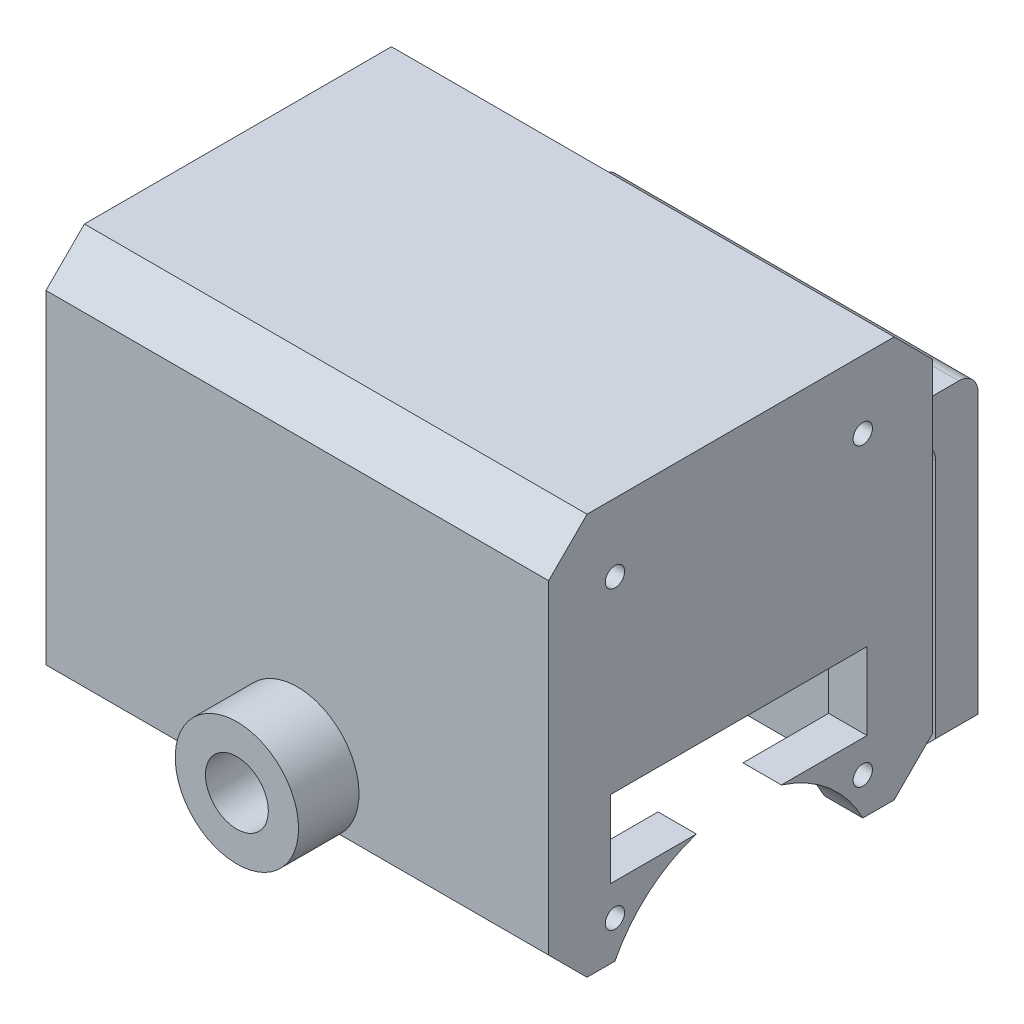
SolidWorks part; units mm, degrees
material "PLA"
ref_plane "Front Plane" through (0, 0, 0) normal (0, 0, 1) x (1, 0, 0)
ref_plane "Top Plane" through (0, 0, 0) normal (0, 1, 0) x (1, 0, 0)
ref_plane "Right Plane" through (0, 0, 0) normal (1, 0, 0) x (0, 0, -1)
sketch "Sketch1" plane through (0, 0, 0) normal (1, 0, 0) x (0, 0, -1)
  line L1 (0, 0) -> (25, 0)
  line L2 (0, 0) -> (0, 30)
  line L3 (0, 30) -> (25, 30)
  line L4 (25, 0) -> (25, 30)
  dimension "D1" = 30
  dimension "D2" = 25
extrude "Boss-Extrude1" add sketch "Sketch1" along normal blind 3.175
sketch "Sketch2" plane through (0, 0, 0) normal (-1, 0, 0) x (0, 0, 1)
  line L1 (-25, 30) -> (0, 30)
  line L2 (-25, 30) -> (-25, 33.175)
  line L3 (-25, 33.175) -> (0, 33.175)
  line L4 (0, 30) -> (0, 33.175)
  dimension "D1" = 3.175
extrude "Boss-Extrude2" add sketch "Sketch2" against normal blind 41.58
sketch "Sketch3" plane through (0, 30, 0) normal (0, -1, 0) x (1, 0, 0)
  line L0 (41.58, 0) -> (3.175, 0) construction
  line L1 (41.58, -25) -> (38.405, -25)
  line L2 (41.58, -25) -> (41.58, 0)
  line L3 (41.58, 0) -> (38.405, 0)
  line L4 (38.405, -25) -> (38.405, 0)
  dimension "D1" = 3.175
extrude "Boss-Extrude3" add sketch "Sketch3" along normal up to surface (30 mm away) up to face at (1.5875, 0, -12.5)
sketch "Sketch4" plane through (0, 0, 0) normal (-1, 0, 0) x (0, 0, 1)
  circle A0 centre (-12.36, -5.21) radius 11.5
  dimension "D1" = 23
extrude "Cut-Extrude1" cut sketch "Sketch4" against normal up to next
sketch "Sketch5" plane through (0, 0, 0) normal (-1, 0, 0) x (0, 0, 1)
  circle A0 centre (-22.61, 3.09) radius 0.8
  circle A1 centre (-22.61, 23.79) radius 0.8
  circle A2 centre (-2.11, 23.79) radius 0.8
  circle A3 centre (-2.11, 3.09) radius 0.8
extrude "Cut-Extrude2" cut sketch "Sketch5" against normal up to next
sketch "Sketch6" plane through (41.58, 0, 0) normal (1, 0, 0) x (0, 0, -1)
  line L1 (1.76, 5.74) -> (22.96, 5.74)
  line L2 (1.76, 5.74) -> (1.76, 12.115)
  line L3 (1.76, 12.115) -> (22.96, 12.115)
  line L4 (22.96, 5.74) -> (22.96, 12.115)
  circle A0 centre (2.11, 3.09) radius 0.8
  circle A1 centre (22.61, 3.09) radius 0.8
  circle A2 centre (22.61, 27.54) radius 0.7999
  circle A3 centre (2.11, 27.54) radius 0.8
extrude "Cut-Extrude3" cut sketch "Sketch6" against normal up to next
sketch "Sketch7" plane through (41.58, 0, 0) normal (1, 0, 0) x (0, 0, -1)
  circle A0 centre (12.36, -5.21) radius 11.5
  dimension "D1" = 23
extrude "Cut-Extrude4" cut sketch "Sketch7" against normal up to next
sketch "Sketch8" plane through (0, 0, 0) normal (0, 0, 1) x (1, 0, 0)
  line L8 (0, 33.175) -> (0, 0)
  line L9 (0, 0) -> (3.175, 0)
  line L10 (3.175, 0) -> (3.175, 30)
  line L11 (3.175, 30) -> (38.405, 30)
  line L12 (38.405, 30) -> (38.405, 0)
  line L13 (38.405, 0) -> (41.58, 0)
  line L14 (41.58, 0) -> (41.58, 33.175)
  line L15 (41.58, 33.175) -> (0, 33.175)
  line L16 (0, 33.175) -> (0, 0)
  line L17 (0, 0) -> (3.175, 0)
  line L18 (3.175, 0) -> (3.175, 30)
  line L19 (3.175, 30) -> (38.405, 30)
  line L20 (38.405, 30) -> (38.405, 0)
  line L21 (38.405, 0) -> (41.58, 0)
  line L22 (41.58, 0) -> (41.58, 33.175)
  line L23 (41.58, 33.175) -> (0, 33.175)
  dimension "D1" = 0
extrude "Boss-Extrude4" add sketch "Sketch8" along normal blind 0.2
sketch "Sketch9" plane through (0, 0, 0.2) normal (0, 0, 1) x (1, 0, 0)
  line L1 (0, 0) -> (41.58, 0)
  line L2 (0, 0) -> (0, 33.175)
  line L3 (0, 33.175) -> (41.58, 33.175)
  line L4 (41.58, 0) -> (41.58, 33.175)
extrude "Boss-Extrude5" add sketch "Sketch9" along normal blind 3.175
sketch "Sketch10" plane through (0, 0, -25) normal (0, 0, -1) x (-1, 0, 0)
  line L8 (0, 0) -> (0, 33.175)
  line L9 (0, 33.175) -> (-41.58, 33.175)
  line L10 (-41.58, 33.175) -> (-41.58, 0)
  line L11 (-41.58, 0) -> (-38.405, 0)
  line L12 (-38.405, 0) -> (-38.405, 30)
  line L13 (-38.405, 30) -> (-3.175, 30)
  line L14 (-3.175, 30) -> (-3.175, 0)
  line L15 (-3.175, 0) -> (0, 0)
  line L16 (0, 0) -> (0, 33.175)
  line L17 (0, 33.175) -> (-41.58, 33.175)
  line L18 (-41.58, 33.175) -> (-41.58, 0)
  line L19 (-41.58, 0) -> (-38.405, 0)
  line L20 (-38.405, 0) -> (-38.405, 30)
  line L21 (-38.405, 30) -> (-3.175, 30)
  line L22 (-3.175, 30) -> (-3.175, 0)
  line L23 (-3.175, 0) -> (0, 0)
  dimension "D1" = 0
extrude "Boss-Extrude6" add sketch "Sketch10" along normal blind 0.2
sketch "Sketch11" plane through (0, 0, -25.2) normal (0, 0, -1) x (-1, 0, 0)
  line L1 (-41.58, 0) -> (0, 0)
  line L2 (-41.58, 0) -> (-41.58, 33.175)
  line L3 (-41.58, 33.175) -> (0, 33.175)
  line L4 (0, 0) -> (0, 33.175)
extrude "Boss-Extrude7" add sketch "Sketch11" along normal blind 3.175
chamfer "Chamfer1" distance 3.175 angle 45 2 edges at (20.79, 33.175, 3.375) (20.79, 33.175, -28.375)
chamfer "Chamfer2" distance 3.175 angle 45 2 edges at (20.79, 0, 3.375) (20.79, 0, -28.375)
sketch "Sketch13" plane through (0, 0, -28.375) normal (0, 0, -1) x (-1, 0, 0)
  line L0 (0, 3.175) -> (0, 30) construction
  line L1 (-35.58, 18.175) -> (-6, 18.175)
  line L3 (-35.58, 21.35) -> (-6, 21.35)
  line L5 (-35.58, 21.35) -> (-35.58, 18.175)
  line L6 (-6, 21.35) -> (-6, 18.175)
  line L7 (-41.58, 30) -> (-41.58, 3.175) construction
  line L9 (-41.58, 3.175) -> (0, 3.175) construction
  dimension "D1" = 3.175
  dimension "D2" = 6
  dimension "D3" = 6
  dimension "D4" = 15
extrude "Boss-Extrude8" add sketch "Sketch13" along normal blind 6.59
sketch "Sketch14" plane through (0, 18.175, 0) normal (0, -1, 0) x (1, 0, 0)
  line L0 (35.58, -34.64) -> (35.58, -39.2524) construction
  line L1 (-0.7092, -38.14) -> (9.3147, -38.14) construction
  line L7 (6, -34.64) -> (6, -38.14)
  line L8 (6, -38.14) -> (35.58, -38.14)
  line L9 (35.58, -34.64) -> (35.58, -38.14)
  line L11 (35.58, -34.965) -> (6, -34.965) construction
  line L12 (6, -34.64) -> (35.58, -34.64)
  dimension "D1" = 3.5
  dimension "D2" = 3.175
  dimension "D3" = 3.5
extrude "Boss-Extrude9" add sketch "Sketch14" against normal up to surface and the other way blind 25 up to face at (20.79, 21.35, -31.67)
chamfer "Chamfer3" distance 3.5 angle 45 2 edges at (35.58, -6.825, -36.39) (6, -6.825, -36.39)
fillet "Fillet1" radius 1.5875 2 edges at (20.79, 21.35, -38.14) (20.79, 18.175, -34.64)
fillet "Fillet2" radius 1.5875 1 edges at (20.79, 21.35, -28.375)
sketch "Sketch16" plane through (0, 0, -38.14) normal (0, 0, -1) x (-1, 0, 0)
  line L0 (-20.79, 19.7625) -> (-20.79, 6.9025) construction
  line L1 (-6, 19.7625) -> (-35.58, 19.7625) construction
  circle A0 centre (-20.79, 6.9025) radius 4.6
  dimension "D2" = 9.2
  dimension "D1" = 12.86
extrude "Cut-Extrude5" cut sketch "Sketch16" against normal up to next
sketch "Sketch20" plane through (0, 0, -34.64) normal (0, 0, 1) x (1, 0, 0)
  circle A0 centre (20.79, 6.9025) radius 4.6 construction
  circle A1 centre (20.79, 6.9025) radius 4.6 construction
  circle A2 centre (20.79, 6.9025) radius 2.6
  circle A3 centre (20.79, 6.9025) radius 8
  dimension "D1" = 5.2
  dimension "D2" = 16
extrude "Boss-Extrude11" add sketch "Sketch20" along normal blind 5
sketch "Sketch21" plane through (0, -6.825, 0) normal (0, -1, 0) x (1, 0, 0)
  line L0 (20.79, -29.64) -> (20.79, -34.64) construction
  line L1 (28.79, -29.64) -> (12.79, -29.64) construction
  line L2 (32.08, -34.64) -> (9.5, -34.64) construction
  circle A0 centre (20.79, -32.14) radius 1.025
  dimension "D1" = 2.05
extrude "Cut-Extrude6" cut sketch "Sketch21" against normal up to surface (25 mm away)
sketch "Sketch23" plane through (0, 0, 3.375) normal (0, 0, 1) x (1, 0, 0)
  circle A2 centre (20.79, 6.9025) radius 2.6
  circle A4 centre (20.79, 6.9025) radius 5.1
  dimension "D1" = 5.2
  dimension "D2" = 10.2
extrude "Boss-Extrude12" add sketch "Sketch23" against normal blind 1.2 and the other way blind 5
